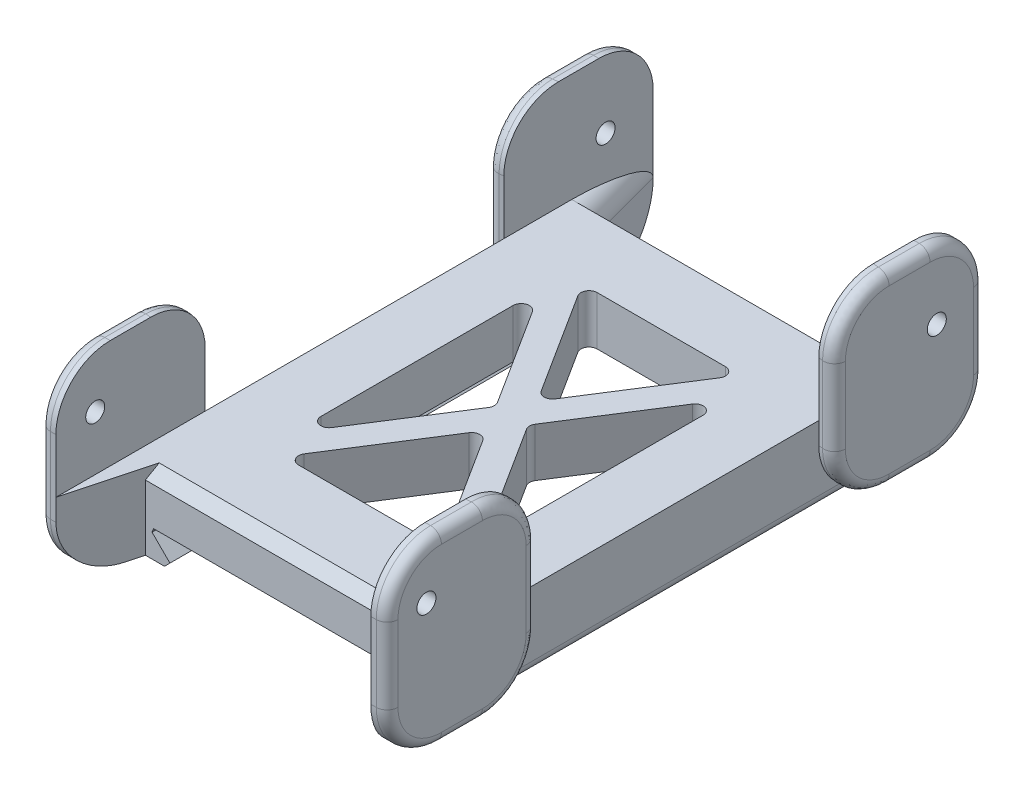
SolidWorks part; units mm, degrees
ref_plane "Front Plane" through (0, 0, 0) normal (0, 0, 1) x (1, 0, 0)
ref_plane "Top Plane" through (0, 0, 0) normal (0, 1, 0) x (1, 0, 0)
ref_plane "Right Plane" through (0, 0, 0) normal (1, 0, 0) x (0, 0, -1)
sketch "Sketch1" plane through (0, 0, 0) normal (0, 0, 1) x (1, 0, 0)
  line L0 (-24, 0) -> (24, 0)
  line L1 (-25, -5) -> (25, -5)
  line L2 (-25, -5) -> (-25, 5)
  line L3 (-25, 5) -> (25, 5)
  line L4 (25, -5) -> (25, 5)
  line L5 (-25, -5) -> (25, 5) construction
  line L6 (-25, 5) -> (25, -5) construction
  line L7 (-24.2929, -0.7071) -> (-20, -5)
  line L8 (0, 0) -> (0, 5) construction
  line L9 (24.2929, -0.7071) -> (20, -5)
  line L10 (-29, -9) -> (-29, 9)
  line L11 (-29, 9) -> (29, 9)
  line L12 (29, -9) -> (29, 9)
  line L13 (-29, -9) -> (29, -9)
  line L14 (-24, 0) -> (-24.2929, -0.7071)
  line L15 (-25, -5) -> (-29, -5)
  line L16 (25, -5) -> (29, -5)
  line L17 (24, 0) -> (24.2929, -0.7071)
  point P0 (0, 0)
  point P6 (-25, 0)
  dimension "D1" = 10
  dimension "D2" = 50
  dimension "D3" = 45
  dimension "D5" = 58
  dimension "D4" = 4
extrude "Boss-Extrude1" add sketch "Sketch1" along normal blind 80 contours L0 L17 L9 L1 L4 L3 L2 L7 L14 | L4 L16 L12 L11 L10 L15 L2 L3 region at (0, 1.964, 0) region at (0, 5.2051, 0)
chamfer "Chamfer1" distance 2 angle 45 2 edges at (-20, -5, 40) (20, -5, 40) first distance on face at (-24.5, -5, 40) first distance on face at (22.1464, -2.8536, 40)
sketch "Sketch3" plane through (0, 0, 0) normal (0, 0, -1) x (-1, 0, 0)
  line L1 (-29, 9) -> (29, 9)
  line L2 (-29, 9) -> (-29, -5)
  line L3 (-29, -5) -> (29, -5)
  line L4 (29, 9) -> (29, -5)
extrude "Boss-Extrude2" add sketch "Sketch3" along normal blind 4
chamfer "Chamfer2" distance 2 angle 45 4 edges at (0, -5, -4) (-29, 2, -4) (0, 9, 80) (0, 9, -4)
sketch "Sketch5" plane through (29, 0, 0) normal (1, 0, 0) x (0, 0, -1)
  circle A0 centre (9.6403, 23.131) radius 1.875
  circle A1 centre (-84.3555, 25.6545) radius 1.875
sketch "Sketch6" plane through (0, 9, 0) normal (0, 1, 0) x (1, 0, 0)
  line L0 (0, 2) -> (0, -78) construction
  line L1 (29, 2) -> (-29, 2) construction
  line L2 (-29, -78) -> (29, -78) construction
  line L3 (29, -10.5) -> (32, 17) construction
  line L4 (29, -78) -> (29, 2) construction
  line L5 (0, -38) -> (29, -38) construction
  line L6 (32.9764, -10.9338) -> (35.9764, 16.5662)
  line L7 (29, -38) -> (32, -38)
  line L8 (29, -38) -> (29, 17)
  line L9 (29, 17) -> (32, 17)
  line L10 (32, -93) -> (32, 17)
  line L11 (25.0236, -10.0662) -> (28.0236, 17.4338)
  line L12 (28.0236, 17.4338) -> (35.9764, 16.5662)
  line L13 (25.0236, -10.0662) -> (32.9764, -10.9338)
  line L14 (-28.0236, 17.4338) -> (-35.9764, 16.5662)
  line L15 (-25.0236, -10.0662) -> (-28.0236, 17.4338)
  line L16 (-32.9764, -10.9338) -> (-35.9764, 16.5662)
  line L17 (-25.0236, -10.0662) -> (-32.9764, -10.9338)
  line L18 (28.0236, -93.4338) -> (35.9764, -92.5662)
  line L19 (25.0236, -65.9338) -> (28.0236, -93.4338)
  line L20 (32.9764, -65.0662) -> (35.9764, -92.5662)
  line L21 (25.0236, -65.9338) -> (32.9764, -65.0662)
  line L22 (-25.0236, -65.9338) -> (-32.9764, -65.0662)
  line L23 (-25.0236, -65.9338) -> (-28.0236, -93.4338)
  line L24 (-28.0236, -93.4338) -> (-35.9764, -92.5662)
  line L25 (-32.9764, -65.0662) -> (-35.9764, -92.5662)
  line L26 (-29, 17) -> (-32, 17)
  line L27 (-29, -93) -> (-29, 17)
  line L28 (29, -38) -> (29, -93)
  line L29 (29, -93) -> (32, -93)
  line L30 (-29, -93) -> (-32, -93)
  line L31 (-32, -93) -> (-32, 17)
  line L32 (-29, -38) -> (-32, -38)
  line L33 (-29, 17) -> (-24.9808, 2)
  line L34 (29, 17) -> (24.9808, 2)
  line L35 (29, -93) -> (24.9808, -78)
  line L36 (-29, -93) -> (-24.9808, -78)
  point P37 (-29, -38)
  line M2 (-29, 2) -> (-29, -78)
  line M3 (-29, -78) -> (29, -78)
  line M4 (29, -78) -> (29, 2)
  line M5 (29, 2) -> (-29, 2)
  dimension "D1" = 55
  dimension "D2" = 3
  dimension "D5" = 15
  dimension "D3" = 4
  dimension "D4" = 4
extrude "Boss-Extrude4" add sketch "Sketch6" along normal blind 20 and the other way up to surface (14 mm away) contours L8 L13 L10 L9 | L8 L34 L11 M5 | L11 L34 M5 | L33 L15 M5 | L33 L27 L15 M5 | L31 L17 L27 L26 M2 | L35 L19 M3 | L35 L28 L19 M3 | L28 L29 L10 L21 M4 | L31 L30 L27 L22 M2 | L27 L36 L23 M3 | L23 L36 M3 region at (30.503, 9, -3.168) region at (28.0097, 9, -7.5133) region at (30.503, 9, 79.168) region at (26.198, 9, -4.8519) region at (28.0097, 9, 83.5133) region at (-26.198, 9, -4.8519) region at (26.198, 9, 80.8519) region at (-28.0097, 9, -7.5133) region at (-30.503, 9, -3.168) region at (-26.198, 9, 80.8519) region at (-28.0097, 9, 83.5133) region at (-30.503, 9, 79.168) other way up to face at (-0.1464, -5, 39.5)
sketch "Sketch8" plane through (-32, 0, 0) normal (-1, 0, 0) x (0, 0, 1)
  circle A0 centre (-8.2348, 16.4764) radius 1.75
  circle A1 centre (85.761, 19) radius 1.75
  dimension "D1" = 3.5
  dimension "D2" = 3.5
extrude "Cut-Extrude2" cut sketch "Sketch8" against normal through all
sketch "Sketch9" plane through (0, 9, 0) normal (0, 1, 0) x (1, 0, 0)
  line L0 (-29, -38) -> (29, -38) construction
  line L1 (-29, -65.5) -> (-29, -10.5) construction
  line L2 (29, -65.5) -> (29, -10.5) construction
  line L3 (0, 2) -> (0, -78)
  line L4 (24.9808, 2) -> (-24.9808, 2) construction
  line L5 (-24.9808, -78) -> (24.9808, -78) construction
  line L6 (-17.5, -10.5) -> (17.5, -65.5)
  line L7 (-11.8042, -65.5) -> (11.8042, -65.5)
  line L8 (-17.5, -55.6923) -> (-17.5, -20.3077)
  line L9 (-11.8042, -10.5) -> (11.8042, -10.5)
  line L10 (17.5, -55.6923) -> (17.5, -20.3077)
  line L11 (-17.5, -65.5) -> (17.5, -10.5) construction
  line L12 (-17.5, -10.5) -> (17.5, -65.5) construction
  line L13 (17.5, -10.5) -> (-17.5, -65.5)
  line L14 (-14.7345, -19.5023) -> (13.0697, -63.1947)
  line L15 (13.0697, -12.8053) -> (-14.7345, -56.4977)
  line L16 (-13.0697, -12.8053) -> (14.7345, -56.4977)
  line L17 (14.7345, -19.5023) -> (-13.0697, -63.1947)
  line L18 (-15.3908, -9.1578) -> (19.6092, -64.1578) construction
  line L19 (15.3908, -9.1578) -> (-19.6092, -64.1578) construction
  line L20 (19.6092, -11.8422) -> (-15.3908, -66.8422) construction
  line L21 (-19.6092, -11.8422) -> (15.3908, -66.8422) construction
  arc A0 (-13.0697, -12.8053) -> (-11.8042, -10.5) centre (-11.8042, -12) cw
  arc A1 (11.8042, -10.5) -> (13.0697, -12.8053) centre (11.8042, -12) cw
  arc A2 (17.5, -20.3077) -> (14.7345, -19.5023) centre (16, -20.3077) ccw
  arc A3 (17.5, -55.6923) -> (14.7345, -56.4977) centre (16, -55.6923) cw
  arc A4 (13.0697, -63.1947) -> (11.8042, -65.5) centre (11.8042, -64) cw
  arc A5 (-11.8042, -65.5) -> (-13.0697, -63.1947) centre (-11.8042, -64) cw
  arc A6 (-14.7345, -56.4977) -> (-17.5, -55.6923) centre (-16, -55.6923) cw
  arc A7 (-14.7345, -19.5023) -> (-17.5, -20.3077) centre (-16, -20.3077) ccw
  point P12 (0, -38)
  dimension "D1" = 1.5
  dimension "D3" = 2.5
  dimension "D4" = 2.5
extrude "Cut-Extrude3" cut sketch "Sketch9" against normal through all contours A3 L10 A2 L17 L16 | A4 L14 L3 L7 | A5 L7 L3 L17 | L14 A7 L8 A6 L15 | A0 L16 L3 L9 | A1 L9 L3 L15 region at (4.7564, 9, 18.1871) region at (-4.7564, 9, 18.1871) region at (12.5321, 9, 38) region at (4.7564, 9, 57.8129) region at (-4.7564, 9, 57.8129) region at (-12.5321, 9, 38)
fillet "Fillet1" radius 1.5 4 edges at (0, 4.5, 33.3434) (2.9633, 4.5, 38) (-2.9633, 4.5, 38) (0, 4.5, 42.6566)
sketch "Sketch10" plane through (-32, 0, 0) normal (-1, 0, 0) x (0, 0, 1)
  circle A0 centre (-8.2348, 16.4764) radius 1.75
  circle A1 centre (85.761, 19) radius 1.75
  dimension "D1" = 3.5
  dimension "D2" = 3.5
fillet "Fillet16" radius 2 2 edges at (29, -5, 38) (-29, -5, 38)
sketch "Sketch11" plane through (0, 29, 0) normal (0, 1, 0) x (1, 0, 0)
  line L0 (-29, -38) -> (29, -38) construction
  line L1 (-29, -65.5) -> (-29, -10.5) construction
  line L2 (29, -65.5) -> (29, -10.5) construction
  line L3 (0, 2) -> (0, -78) construction
  line L4 (24.9808, 2) -> (-24.9808, 2) construction
  line L5 (-24.9808, -78) -> (24.9808, -78) construction
  line L6 (24.9808, 2) -> (29, 17)
  line L7 (29, 17) -> (29, 2)
  line L8 (29, 2) -> (24.9808, 2)
  line L9 (-29, 17) -> (-29, 2)
  line L10 (-24.9808, 2) -> (-29, 17)
  line L11 (-29, 2) -> (-24.9808, 2)
  line L12 (-29, -78) -> (-24.9808, -78)
  line L13 (-24.9808, -78) -> (-29, -93)
  line L14 (-29, -93) -> (-29, -78)
  line L15 (29, -78) -> (24.9808, -78)
  line L16 (29, -93) -> (29, -78)
  line L17 (24.9808, -78) -> (29, -93)
extrude "Cut-Extrude4" cut sketch "Sketch11" against normal up to surface (20 mm away) up to face at (0, 9, 38)
fillet "Fillet17" radius 10 16 edges at (-29.5, -5, 65.4455) (-30.5, 29, 65.3364) (-29.5, -5, 10.5545) (-30.5, 29, 10.6636) (-30.5, 29, -17) (-30.5, -5, -17) (30.5, -5, -17) (30.5, 29, -17) (30.5, 29, 10.6636) (29.5, -5, 10.5545) (29.5, -5, 65.4455) (30.5, 29, 65.3364) (30.5, 29, 93) (30.5, -5, 93) (-30.5, -5, 93) (-30.5, 29, 93)
fillet "Fillet18" radius 2 32 edges at (32, -2.0711, 7.881) (32, -5, -3.116) (32, -2.0711, -14.0711) (32, 12, -17) (32, 26.0711, -14.0711) (32, 29, -3.116) (32, 26.0711, 7.881) (32, 26.0711, 90.0711) (32, 29, 79.116) (32, 26.0711, 68.119) (32, 12, 65.1727) (32, -2.0711, 68.119) (32, -5, 79.116) (32, -2.0711, 90.0711) (-32, 26.0711, 7.881) (-32, 29, -3.116) (-32, 26.0711, -14.0711) (-32, 12, -17) (-32, -2.0711, -14.0711) (-32, -5, -3.116) (-32, -2.0711, 7.881) (-32, -2.0711, 90.0711) (-32, -5, 79.116) (-32, -2.0711, 68.119) (-32, 12, 65.1727) (-32, 26.0711, 68.119) (-32, 29, 79.116) (-32, 26.0711, 90.0711) (32, 12, 10.8273) (32, 12, 93) (-32, 12, 10.8273) (-32, 12, 93)
fillet "Fillet19" radius 4 2 edges at (-26.9904, 9, -9.5) (26.9904, 9, -9.5)
